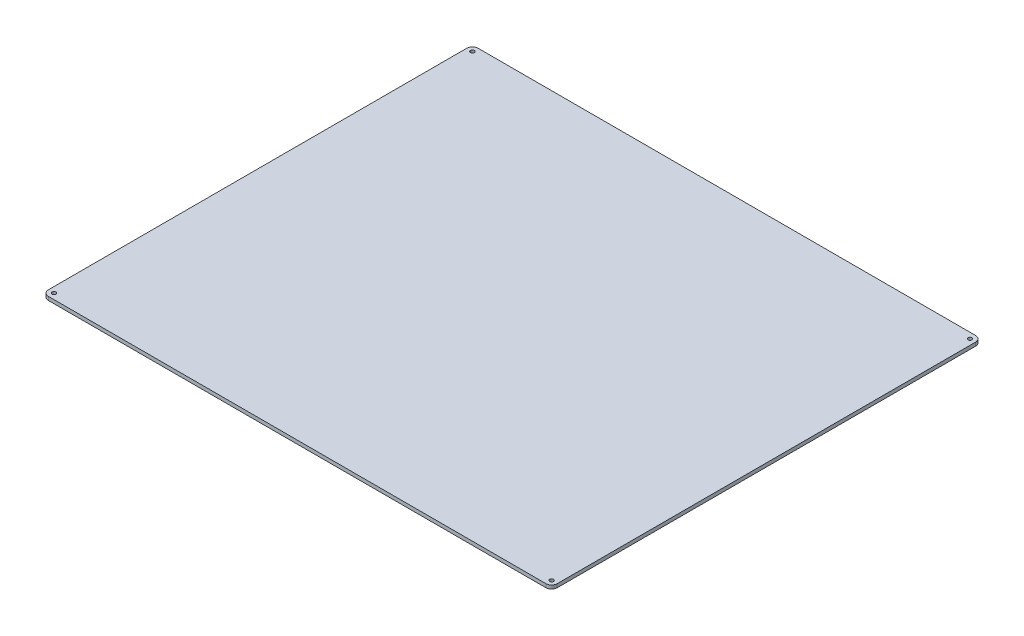
SolidWorks part; units mm, degrees
ref_plane "Front Plane" through (0, 0, 0) normal (0, 0, 1) x (1, 0, 0)
ref_plane "Top Plane" through (0, 0, 0) normal (0, 1, 0) x (1, 0, 0)
ref_plane "Right Plane" through (0, 0, 0) normal (1, 0, 0) x (0, 0, -1)
sketch "Sketch2" plane through (0, 0, 0) normal (0, 1, 0) x (1, 0, 0)
  line L1 (0, 0) -> (450, 0)
  line L2 (0, 0) -> (0, 380)
  line L3 (0, 380) -> (450, 380)
  line L4 (450, 0) -> (450, 380)
  dimension "D1" = 380
  dimension "D2" = 450
extrude "Boss-Extrude1" add sketch "Sketch2" along normal blind 3.175
hole_wizard "M3 Clearance Hole1" positions "3DSketch1" profile "Sketch3" hole size "M3" standard "ISO" end condition through all
sketch3d "3DSketch1"
  line L7 (5, 3.175, -375) -> (0, 3.175, -375) construction
  line L8 (0, 3.175, -380) -> (0, 3.175, 0) construction
  line L10 (5, 3.175, -375) -> (5, 3.175, -380) construction
  line L11 (450, 3.175, -380) -> (0, 3.175, -380) construction
  line L12 (445, 3.175, -380) -> (445, 3.175, -375) construction
  line L13 (445, 3.175, -375) -> (450, 3.175, -375) construction
  line L14 (450, 3.175, 0) -> (450, 3.175, -380) construction
  line L16 (0, 3.175, -5) -> (5, 3.175, -5) construction
  line L17 (5, 3.175, -5) -> (5, 3.175, 0) construction
  line L18 (0, 3.175, 0) -> (450, 3.175, 0) construction
  line L20 (450, 3.175, -5) -> (445, 3.175, -5) construction
  line L21 (445, 3.175, -5) -> (445, 3.175, 0) construction
  point P0 (5, 3.175, -375)
  point P44 (445, 3.175, -375)
  point P46 (5, 3.175, -5)
  point P48 (445, 3.175, -5)
  dimension "D1" = 440
  dimension "D2" = 370
sketch "Sketch3" plane through (5, 3.175, -375) normal (1, 0, 0) x (0, 0, 1)
  line L0 (0, 0) -> (0, 3.175)
  line L1 (0, 3.175) -> (1.7, 3.175)
  line L2 (1.7, 3.175) -> (1.7, 0)
  line L5 (1.7, 0) -> (0, 0)
  line L11 (0, -6.35) -> (0, 107.95) construction
  dimension "Thru Hole Dia." = 3.4
  dimension "Thru Hole Depth" = 3.175
fillet "Fillet1" radius 5 4 edges at (0, 1.5875, 0) (450, 1.5875, 0) (0, 1.5875, -380) (450, 1.5875, -380)
